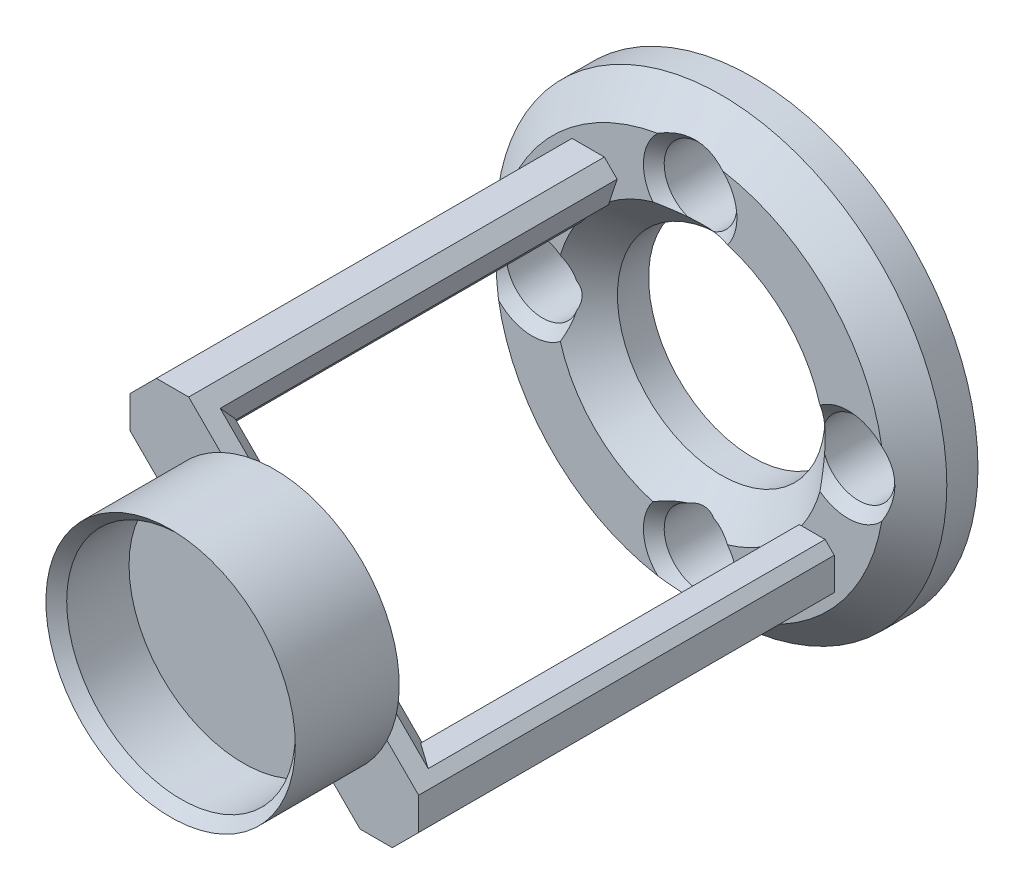
SolidWorks part; units mm, degrees
ref_plane "Front Plane" through (0, 0, 0) normal (0, 0, 1) x (1, 0, 0)
ref_plane "Top Plane" through (0, 0, 0) normal (0, 1, 0) x (1, 0, 0)
ref_plane "Right Plane" through (0, 0, 0) normal (1, 0, 0) x (0, 0, -1)
sketch "Sketch1" plane through (0, 0, 0) normal (0, 0, 1) x (1, 0, 0)
  circle A0 centre (0, 0) radius 10.85
  circle A1 centre (0, 7.6) radius 1.75
  circle A2 centre (0, -7.6) radius 1.75
  circle A3 centre (7.6, 0) radius 1.75
  circle A4 centre (-7.6, 0) radius 1.75
  circle A5 centre (0, 0) radius 5
extrude "Boss-Extrude1" add sketch "Sketch1" along normal blind 3
sketch "Sketch3" plane through (0, 0, 3) normal (0, 0, 1) x (1, 0, 0)
  line L0 (5.7166, -2.8972) -> (7.7117, -4.8923)
  line L6 (-7.7264, 4.9071) -> (-5.7166, 2.8972)
  line L8 (-4.9071, 7.7264) -> (-2.8972, 5.7166)
  line L9 (-7.7264, 4.9071) -> (-4.9071, 7.7264)
  line L10 (2.8972, -5.7166) -> (4.8923, -7.7117)
  line L11 (4.8923, -7.7117) -> (7.7117, -4.8923)
  arc A3 (2.8972, -5.7166) -> (5.7166, -2.8972) centre (0, 0) ccw
  arc A4 (-2.8972, 5.7166) -> (-5.7166, 2.8972) centre (0, 0) ccw
  point P0 (0, 0)
  point P4 (-5.477, 5.269)
  point P9 (0, 0)
  point P10 (5.477, -5.269)
chamfer "Chamfer4" distance 1.5 angle 45 1 edges at (10.85, 0, 3)
chamfer "Chamfer6" distance 1.5 angle 45 1 edges at (5, 0, 3)
chamfer "Chamfer7" distance 0.5 angle 45 8 edges at (8.2798, 1.6126, 3) (8.2798, -1.6126, 3) (-1.6126, 8.2798, 3) (1.6126, 8.2798, 3) (1.6126, -8.2798, 3) (-1.6126, -8.2798, 3) (-8.2798, -1.6126, 3) (-8.2798, 1.6126, 3)
extrude "Boss-Extrude7" add sketch "Sketch3" along normal blind 20
sketch "Sketch7" plane through (6.302, -6.302, 0) normal (0.7071, -0.7071, 0) x (0, 0, -1)
  line L0 (-23, 1.9936) -> (-3, 1.9936) construction
  line L1 (-23, -1.9936) -> (-21, -1.9936)
  line L2 (-23, -1.9936) -> (-23, 1.9936)
  line L3 (-23, 1.9936) -> (-21, 1.9936)
  line L4 (-21, -1.9936) -> (-21, 1.9936)
  dimension "D1" = 2
extrude "Boss-Extrude8" add sketch "Sketch7" against normal up to surface (17.8456 mm away)
chamfer "Chamfer9" distance 1.1 angle 45 10 edges at (1.4097, 1.4097, 21) (-1.4097, -1.4097, 21) (-2.8972, 5.7166, 12) (-5.7166, 2.8972, 12) (2.8972, -5.7166, 12) (5.7166, -2.8972, 12) (7.7117, -4.8923, 13) (4.8923, -7.7117, 13) (-4.9071, 7.7264, 13) (-7.7264, 4.9071, 13)
sketch "Sketch10" plane through (0, 0, 23) normal (0, 0, 1) x (1, 0, 0)
  circle A0 centre (0, 0) radius 6
  dimension "D1" = 12
extrude "Boss-Extrude12" add sketch "Sketch10" along normal blind 1.5
sketch "Sketch11" plane through (0, 0, 24.5) normal (0, 0, 1) x (1, 0, 0)
  circle A0 centre (0, 0) radius 6
  circle A1 centre (0, 0) radius 5.5
  dimension "D1" = 11
extrude "Boss-Extrude13" add sketch "Sketch11" along normal blind 4
chamfer "Chamfer12" distance 1 angle 45 1 edges at (5.5, 0, 28.5)
